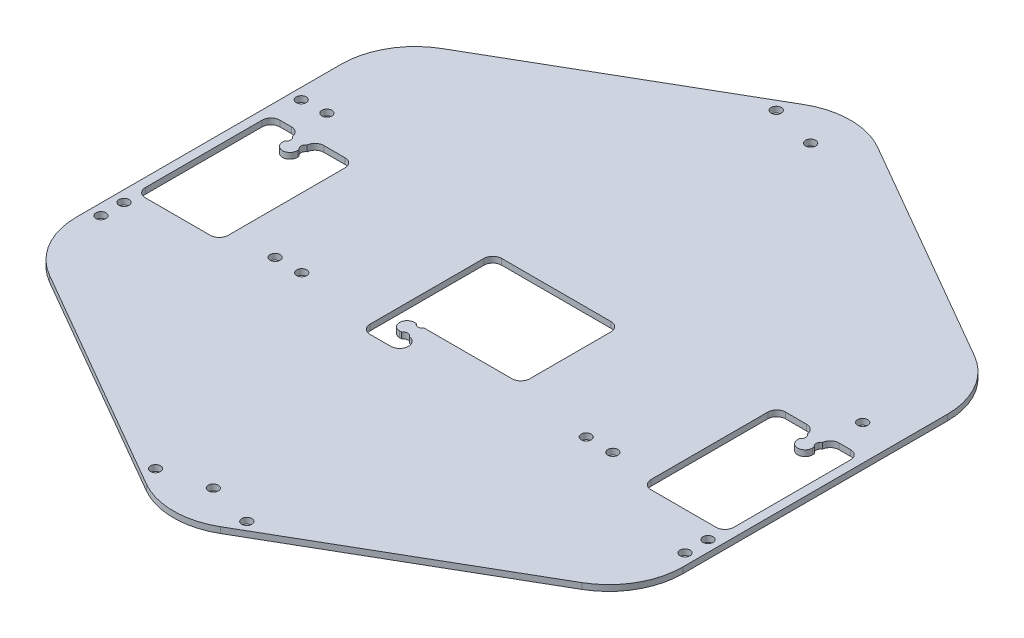
SolidWorks part; units mm, degrees
material "Alu"
ref_plane "Plan de face" through (0, 0, 0) normal (0, 0, 1) x (1, 0, 0)
ref_plane "Plan de dessus" through (0, 0, 0) normal (0, 1, 0) x (1, 0, 0)
ref_plane "Plan de droite" through (0, 0, 0) normal (1, 0, 0) x (0, 0, -1)
sketch "Esquisse1" plane through (0, 0, 0) normal (0, 1, 0) x (1, 0, 0)
  line L0 (-102.5, 0) -> (102.5, 0) construction
  line L1 (-102.5, 59.1784) -> (-102.5, -59.1784)
  line L2 (102.5, 59.1784) -> (102.5, -59.1784)
  line L3 (-102.5, -59.1784) -> (0, -118.3568)
  line L5 (0, -118.3568) -> (102.5, -59.1784)
  line L6 (102.5, 59.1784) -> (0, 118.3568)
  line L8 (0, 118.3568) -> (-102.5, 59.1784)
  line L9 (0, -118.3568) -> (0, 118.3568) construction
  line L10 (-102.5, 59.1784) -> (102.5, 59.1784) construction
  line L11 (102.5, -59.1784) -> (-102.5, -59.1784) construction
  circle A1 centre (0, 0) radius 102.5 construction
  point P13 (0, 0)
  dimension "D5" = 118.3568
  dimension "D1" = 205
  dimension "D6" = 118.3568
extrude "Boss.-Extru.1" add sketch "Esquisse1" along normal blind 2
sketch "Esquisse2" plane through (0, 2, 0) normal (0, 1, 0) x (1, 0, 0)
  line L0 (0, 0) -> (0, -118.3568) construction
  line L1 (-99.5, 18) -> (-71.5, 18)
  line L2 (-99.5, 18) -> (-99.5, -27.5)
  line L3 (-99.5, -27.5) -> (-71.5, -27.5)
  line L4 (71.5, 18) -> (71.5, -27.5)
  line L5 (99.5, -27.5) -> (71.5, -27.5)
  line L6 (99.5, 18) -> (99.5, -27.5)
  line L7 (99.5, 18) -> (71.5, 18)
  line L12 (-102.5, 59.1784) -> (-102.5, -59.1784) construction
  line L18 (-71.5, 18) -> (-71.5, -27.5)
  line L30 (0, 0) -> (-71.5, 0) construction
  line L31 (-71.5, 0) -> (-102.5, 0) construction
  dimension "D1" = 18
  dimension "D2" = 31
  dimension "D3" = 45.5
  dimension "D4" = 3
extrude "Enlèv. mat.-Extru.1" cut sketch "Esquisse2" against normal through all
sketch "Esquisse10" plane through (0, 2, 0) normal (0, 1, 0) x (1, 0, 0)
  line L0 (89.6, 18) -> (89.6, 12)
  line L2 (84.6, 18) -> (89.6, 18)
  line L3 (84.6, 12) -> (84.6, 18)
  line L4 (87.1, 12) -> (87.1, 18) construction
  line L7 (99.5, 18) -> (71.5, 18) construction
  line L9 (102.5, -59.1784) -> (102.5, 59.1784) construction
  arc A0 (84.6, 12) -> (89.6, 12) centre (87.1, 12) ccw
  point P10 (87.1, 15)
  dimension "D1" = 15.4
  dimension "D2" = 6
  dimension "D3" = 5
extrude "Boss.-Extru.2" add sketch "Esquisse10" against normal up to surface (2 mm away) up to face at (85.5, 0, 4.75)
sketch "Esquisse11" plane through (0, 2, 0) normal (0, 1, 0) x (1, 0, 0)
  line L0 (87.1, 14) -> (83.75, 14) construction
  line L1 (84.6, 18) -> (89.6, 18) construction
  line L2 (87.1, 18) -> (87.1, 14) construction
  line L3 (87.1, 14) -> (90.45, 14) construction
  line L4 (84.6, 18) -> (84.6, 12) construction
  circle A0 centre (83.75, 14) radius 1.6
  circle A1 centre (90.45, 14) radius 1.6
  point P12 (85.35, 14)
  point P13 (88.85, 14)
  dimension "D2" = 3.2
  dimension "D1" = 3.5
  dimension "D3" = 4
extrude "Enlèv. mat.-Extru.2" cut sketch "Esquisse11" against normal through all
mirror "Symétrie4" about plane through (0, 0, 0) normal (1, 0, 0) of "Enlèv. mat.-Extru.2", "Boss.-Extru.2"
fillet "Congé7" radius 3 12 edges at (-89.6, 1, -18) (-71.5, 1, -18) (-84.6, 1, -18) (71.5, 1, -18) (84.6, 1, -18) (89.6, 1, -18) (-99.5, 1, -18) (-99.5, 1, 27.5) (-71.5, 1, 27.5) (99.5, 1, 27.5) (71.5, 1, 27.5) (99.5, 1, -18)
fillet "Congé8" radius 25 6 edges at (102.5, 1, 59.1784) (-102.5, 1, 59.1784) (-102.5, 1, -59.1784) (102.5, 1, -59.1784) (0, 1, -118.3568) (0, 1, 118.3568)
hole_wizard "Diamètre du perçage Ø3.4 (3.4)2" positions "Esquisse27" profile "Esquisse26" hole size "Ø3.4" standard "Iso"
sketch "Esquisse27" plane through (0, 2, 0) normal (0, 1, 0) x (-1, 0, 0)
  line L13 (0, 101) -> (0, -101) construction
  point P0 (0, -101)
  point P7 (0, 101)
  dimension "D1" = 101
sketch "Esquisse26" plane through (0, 2, -101) normal (1, 0, 0) x (0, 0, 1)
  line L0 (0, 0) -> (0, 4.0215)
  line L1 (0, 4.0215) -> (1.7, 3)
  line L2 (1.7, 3) -> (1.7, 0)
  line L5 (1.7, 0) -> (0, 0)
  line L10 (0, 4.0215) -> (-1.7, 3) construction
  line L11 (0, -6.35) -> (0, 107.95) construction
  dimension "Diamètre du perçage" = 3.4
  dimension "Profondeur du perçage" = 3
  dimension "Angle de pointe" = 118
sketch "Esquisse32" plane through (0, 2, 0) normal (0, 1, 0) x (1, 0, 0)
  line L6 (90, 66.3953) -> (12.5, 111.1399)
  line L7 (-12.5, 111.1399) -> (-90, 66.3953)
  line L8 (-102.5, 44.7446) -> (-102.5, -44.7446)
  line L9 (-90, -66.3953) -> (-12.5, -111.1399)
  line L10 (12.5, -111.1399) -> (90, -66.3953)
  line L11 (102.5, -44.7446) -> (102.5, 44.7446)
  line L12 (90, 66.3953) -> (12.5, 111.1399)
  line L13 (-12.5, 111.1399) -> (-90, 66.3953)
  line L14 (-102.5, 44.7446) -> (-102.5, -44.7446)
  line L15 (-90, -66.3953) -> (-12.5, -111.1399)
  line L16 (12.5, -111.1399) -> (90, -66.3953)
  line L17 (102.5, -44.7446) -> (102.5, 44.7446)
  arc A6 (12.5, 111.1399) -> (-12.5, 111.1399) centre (0, 89.4893) ccw
  arc A7 (-90, 66.3953) -> (-102.5, 44.7446) centre (-77.5, 44.7446) ccw
  arc A8 (-102.5, -44.7446) -> (-90, -66.3953) centre (-77.5, -44.7446) ccw
  arc A9 (-12.5, -111.1399) -> (12.5, -111.1399) centre (0, -89.4893) ccw
  arc A10 (90, -66.3953) -> (102.5, -44.7446) centre (77.5, -44.7446) ccw
  arc A11 (102.5, 44.7446) -> (90, 66.3953) centre (77.5, 44.7446) ccw
  arc A12 (12.5, 111.1399) -> (-12.5, 111.1399) centre (0, 89.4893) ccw
  arc A13 (-90, 66.3953) -> (-102.5, 44.7446) centre (-77.5, 44.7446) ccw
  arc A14 (-102.5, -44.7446) -> (-90, -66.3953) centre (-77.5, -44.7446) ccw
  arc A15 (-12.5, -111.1399) -> (12.5, -111.1399) centre (0, -89.4893) ccw
  arc A16 (90, -66.3953) -> (102.5, -44.7446) centre (77.5, -44.7446) ccw
  arc A17 (102.5, 44.7446) -> (90, 66.3953) centre (77.5, 44.7446) ccw
  dimension "D1" = 0
hole_wizard "Dégagement M31" positions "Esquisse34" profile "Esquisse33" hole size "M3" standard "ISO" end condition through all
sketch "Esquisse34" plane through (0, 0, 0) normal (0, -1, 0) x (-1, 0, 0)
  line L0 (0, 0) -> (0, -35.3647) construction
  point P9 (48.1, -23)
  point P12 (57.1, -23)
  point P19 (-57.1, -23)
  point P20 (-48.1, -23)
sketch "Esquisse33" plane through (-48.1, 0, 23) normal (1, 0, 0) x (0, 0, -1)
  line L0 (0, 0) -> (0, 2)
  line L1 (0, 2) -> (1.7, 2)
  line L2 (1.7, 2) -> (1.7, 0)
  line L5 (1.7, 0) -> (0, 0)
  line L11 (0, -6.35) -> (0, 107.95) construction
  dimension "Diamètre du perçage jusqu'au prochain" = 3.4
  dimension "Profondeur du perçage jusqu'au prochain" = 2
hole_wizard "Dégagement M33" positions "Esquisse36" profile "Esquisse35" hole size "M3" standard "ISO"
sketch "Esquisse36" plane through (0, 0, 0) normal (0, -1, 0) x (-1, 0, 0)
  point P0 (15.4381, -105.1135)
  point P3 (-15.4381, -105.1135)
  point P6 (-98.75, -40.25)
  point P9 (-98.75, -32.45)
  point P12 (-90.5945, 27.9945)
  point P24 (15.4381, 104.7893)
  point P27 (98.85, 27.55)
  point P30 (90.5945, 27.9945)
  point P33 (98.75, -40.25)
  point P36 (98.75, -32.45)
sketch "Esquisse35" plane through (-15.4381, 0, 105.1135) normal (1, 0, 0) x (0, 0, -1)
  line L0 (0, 0) -> (0, 8.0215)
  line L1 (0, 8.0215) -> (1.7, 7)
  line L2 (1.7, 7) -> (1.7, 0)
  line L5 (1.7, 0) -> (0, 0)
  line L10 (0, 8.0215) -> (-1.7, 7) construction
  line L11 (0, -6.35) -> (0, 107.95) construction
  dimension "Diamètre du perçage" = 3.4
  dimension "Profondeur du perçage" = 7
  dimension "Angle de pointe" = 118
sketch "Esquisse38" plane through (0, 2, 0) normal (0, 1, 0) x (1, 0, 0)
  line L0 (0, 15) -> (0, -18.5) construction
  line L1 (21.5, -18.5) -> (-8.5, -18.5)
  line L2 (21.5, -18.5) -> (21.5, 15)
  line L3 (21.5, 15) -> (-21.5, 15)
  line L4 (-21.5, -29.5) -> (-21.5, 15)
  line L5 (-8.5, -18.5) -> (-8.5, -29.5)
  line L6 (-8.5, -29.5) -> (-21.5, -29.5)
  dimension "D1" = 43
  dimension "D2" = 18.5
  dimension "D3" = 15
  dimension "D4" = 11
  dimension "D5" = 8.5
extrude "Enlèv. mat.-Extru.3" cut sketch "Esquisse38" against normal through all
sketch "Esquisse39" plane through (0, 2, 0) normal (0, 1, 0) x (1, 0, 0)
  line L4 (-8.5, -21) -> (-14.5, -21) construction
  line L5 (-8.5, -29.5) -> (-8.5, -18.5) construction
  line L6 (-8.5, -23.5) -> (-14.5, -23.5)
  line L7 (-8.5, -18.5) -> (-14.5, -18.5)
  arc A1 (-8.5, -23.5) -> (-8.5, -18.5) centre (-8.5, -21) ccw
  arc A2 (-14.5, -18.5) -> (-14.5, -23.5) centre (-14.5, -21) ccw
  point P11 (-11.5, -21)
  dimension "D3" = 5
  dimension "D4" = 6
extrude "Boss.-Extru.3" add sketch "Esquisse39" against normal up to surface (2 mm away) up to face at (-2.8333, 0, 11)
sketch "Esquisse40" plane through (0, 2, 0) normal (0, 1, 0) x (1, 0, 0)
  line L4 (-12.5, -17.65) -> (-12.5, -21) construction
  line L5 (-8.5, -21) -> (-14.5, -21) construction
  line L6 (-12.5, -21) -> (-12.5, -24.35) construction
  circle A2 centre (-12.5, -17.65) radius 1.6
  circle A3 centre (-12.5, -24.35) radius 1.6
  dimension "D4" = 3.2
  dimension "D5" = 3.5
  dimension "D6" = 4
extrude "Enlèv. mat.-Extru.4" cut sketch "Esquisse40" against normal through all
fillet "Congé9" radius 3 6 edges at (21.5, 1, 18.5) (-21.5, 1, -15) (21.5, 1, -15) (-21.5, 1, 29.5) (-8.5, 1, 29.5) (-8.5, 1, 23.5)
